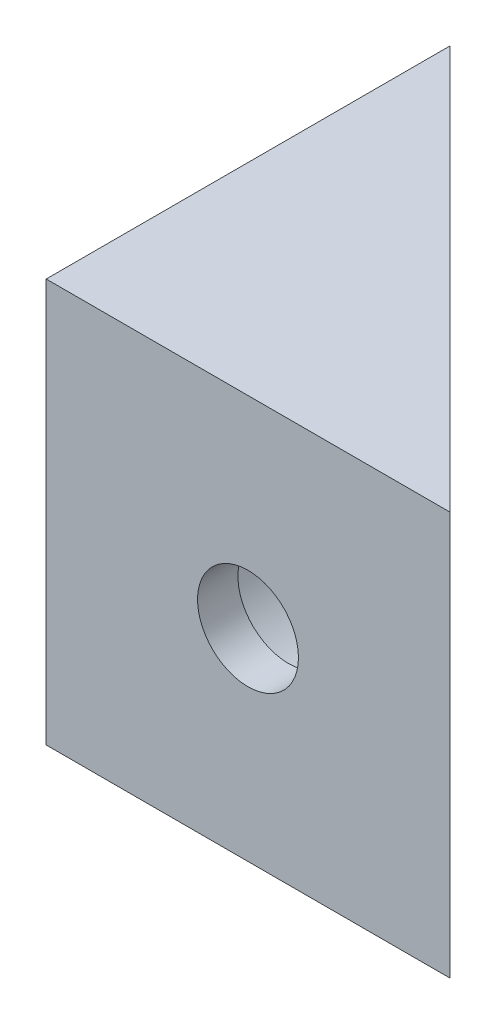
SolidWorks part; units mm, degrees
ref_plane "Front Plane" through (0, 0, 0) normal (0, 0, 1) x (1, 0, 0)
ref_plane "Top Plane" through (0, 0, 0) normal (0, 1, 0) x (1, 0, 0)
ref_plane "Right Plane" through (0, 0, 0) normal (1, 0, 0) x (0, 0, -1)
sketch "Sketch1" plane through (0, 0, 0) normal (0, 1, 0) x (1, 0, 0)
  line L0 (0, 0) -> (0, 20)
  line L1 (0, 20) -> (20, 0)
  line L2 (20, 0) -> (0, 0)
  dimension "D1" = 20
  dimension "D2" = 20
extrude "Boss-Extrude1" add sketch "Sketch1" along normal blind 20
sketch "Sketch2" plane through (0, 0, 0) normal (0, 0, 1) x (1, 0, 0)
  line L0 (0, 20) -> (20, 0) construction
  circle A0 centre (10, 10) radius 2.5
  dimension "D1" = 5
extrude "Cut-Extrude1" cut sketch "Sketch2" against normal through all
sketch "Sketch3" plane through (0, 0, 0) normal (-1, 0, 0) x (0, 0, 1)
  line L0 (-20, 20) -> (0, 0) construction
  circle A0 centre (-10, 10) radius 2.5
  dimension "D1" = 5
extrude "Cut-Extrude2" cut sketch "Sketch3" against normal through all contours A0
sketch "Sketch4" plane through (0, 0, 0) normal (-1, 0, 0) x (0, 0, 1)
  circle A0 centre (-10, 10) radius 5
  dimension "D1" = 10
extrude "Cut-Extrude3" cut sketch "Sketch4" against normal through all from offset 2 contours A0 offset against normal yes
sketch "Sketch5" plane through (0, 0, 0) normal (0, 0, 1) x (1, 0, 0)
  circle A0 centre (10, 10) radius 5
  dimension "D1" = 10
extrude "Cut-Extrude4" cut sketch "Sketch5" against normal blind 20 from offset 2 offset against normal yes
